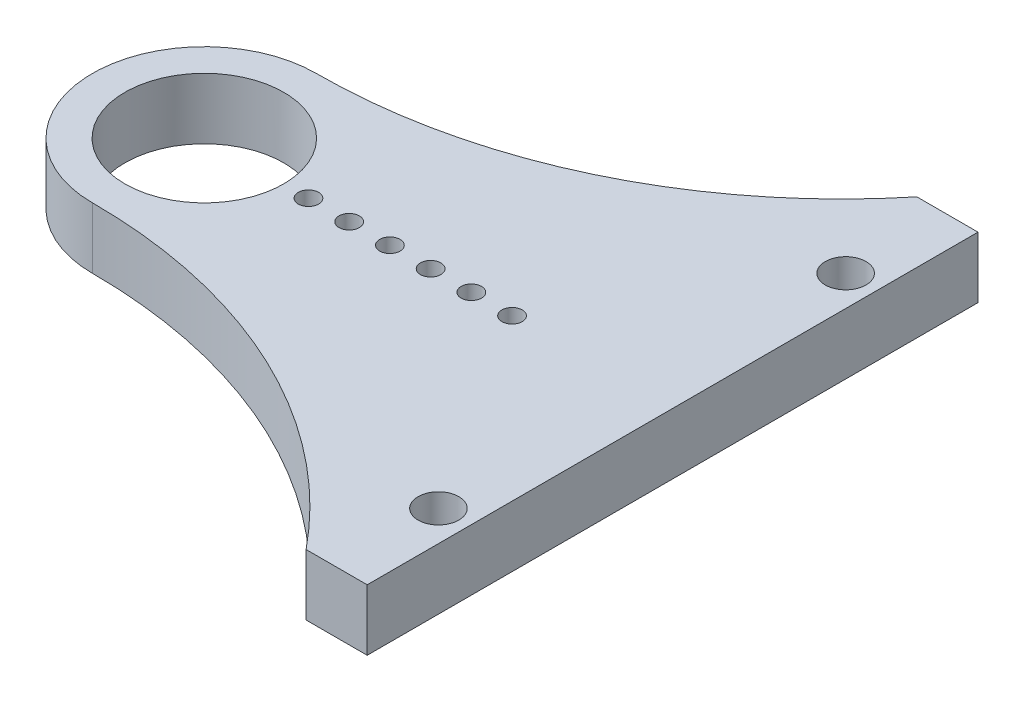
SolidWorks part; units mm, degrees
material "ABS"
ref_plane "Front Plane" through (0, 0, 0) normal (0, 0, 1) x (1, 0, 0)
ref_plane "Top Plane" through (0, 0, 0) normal (0, 1, 0) x (1, 0, 0)
ref_plane "Right Plane" through (0, 0, 0) normal (1, 0, 0) x (0, 0, -1)
sketch "Sketch1" plane through (0, 0, 0) normal (0, 1, 0) x (1, 0, 0)
  line L0 (-43.4243, 47.0808) -> (-41.3374, 46.963)
  line L1 (-43.4243, 41.4808) -> (-41.3374, 41.5986)
  line L5 (-43.4243, 47.0808) -> (-31.0239, 46.3808)
  line L6 (-46.1391, 44.2808) -> (-31.0239, 44.2808) construction
  line L7 (-31.0239, 42.1808) -> (-43.4243, 41.4808)
  line L8 (-50.0391, 44.2808) -> (-33.2736, 44.2808) construction
  line L9 (-43.4243, 47.0808) -> (-43.4243, 41.4808) construction
  line L10 (-31.0239, 46.3808) -> (-31.0239, 42.1808) construction
  line L11 (-50.7391, 44.2808) -> (-23.1391, 44.2808) construction
  line L12 (-50.7391, 59.2808) -> (-23.1391, 59.2808)
  line L13 (-50.7391, 59.2808) -> (-50.7391, 29.2808)
  line L14 (-50.7391, 29.2808) -> (-23.1391, 29.2808)
  line L15 (-23.1391, 59.2808) -> (-23.1391, 29.2808)
  line L16 (-26.1391, 29.2808) -> (-23.1391, 29.2808) construction
  line L17 (-23.1391, 59.2808) -> (-26.1391, 59.2808)
  line L18 (-23.1391, 59.2808) -> (-23.1391, 29.2808)
  line L19 (-23.1391, 29.2808) -> (-26.1391, 29.2808)
  line L20 (-26.1391, 59.2808) -> (-26.1391, 29.2808)
  line L21 (-24.6391, 29.2808) -> (-24.6391, 59.2808) construction
  circle A0 centre (-46.1391, 44.2808) radius 5.5
  arc A1 (-46.1391, 49.7808) -> (-26.1391, 59.2808) centre (-46.1391, 75.5834) ccw
  arc A2 (-46.1391, 38.7808) -> (-26.1391, 29.2808) centre (-46.1391, 12.9782) cw
  circle A4 centre (-46.1391, 44.2808) radius 3.9
  arc A5 (-31.0239, 46.3808) -> (-31.0239, 42.1808) centre (-31.1424, 44.2808) cw
  circle A6 centre (-31.0239, 44.2808) radius 0.5
  circle A7 centre (-33.0239, 44.2808) radius 0.5
  circle A8 centre (-35.0239, 44.2808) radius 0.5
  circle A9 centre (-37.0239, 44.2808) radius 0.5
  circle A10 centre (-39.0239, 44.2808) radius 0.5
  circle A11 centre (-41.0239, 44.2808) radius 0.5
  circle A12 centre (-46.1391, 44.2808) radius 2.4
  circle A13 centre (-46.1391, 44.2808) radius 1.6
  circle A14 centre (-24.6391, 54.2808) radius 1
  circle A15 centre (-24.6391, 34.2808) radius 1
  point P28 (-29.0391, 44.2808)
  point P40 (-33.9783, 44.2808)
  dimension "D4" = 30
  dimension "D6" = 1
  dimension "D8" = 4.2
  dimension "D9" = 12.4004
  dimension "D5" = 5.6
  dimension "D7" = 21
  dimension "D13" = 20
  dimension "D2" = 11
  dimension "D3" = 20
  dimension "D11" = 4.6
  dimension "D12" = 3
extrude "Boss-Extrude1" add sketch "Sketch1" against normal blind 3 contours A4 L0 A0 L1 | L5 A5 L7 A0 A2 L20 A1 | L12 L20 L14 L15 A14 A15 | L13 A0 region at (-50.1838, 0, -44.2808) region at (-43.1729, 0, -49.3353) region at (-51.1017, 0, -44.2808) region at (-24.6391, 0, -44.2808)
extrude "Boss-Extrude2" add sketch "Sketch1<3>" against normal blind 1.5 contours A5 L5 A4 L7 A11 A10 A9 A8 A7 A6 | A4 L1 A0 L0 region at (-41.8184, 0, -44.2808) region at (-36.1882, 0, -46.5379)
sketch "Sketch1<3>" plane through (0, 0, 0) normal (0, 1, 0) x (1, 0, 0) same geometry as "Sketch1"
